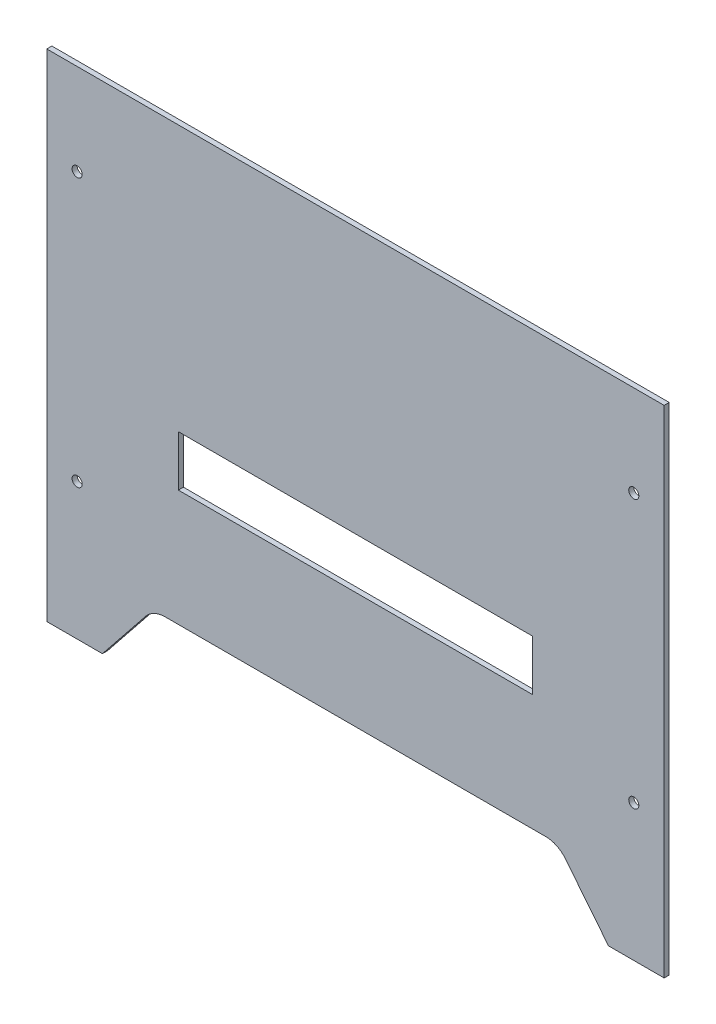
SolidWorks part; units mm, degrees
ref_plane "前视基准面" through (0, 0, 0) normal (0, 0, 1) x (1, 0, 0)
ref_plane "上视基准面" through (0, 0, 0) normal (0, 1, 0) x (1, 0, 0)
ref_plane "右视基准面" through (0, 0, 0) normal (1, 0, 0) x (0, 0, -1)
sketch "Sketch1" plane through (0, 0, 0) normal (0, 0, 1) x (1, 0, 0)
  line L0 (0, -98) -> (0, 0) construction
  line L1 (-122, -98) -> (122, -98) construction
  line L2 (-122, -98) -> (-122, 98)
  line L3 (-122, 98) -> (122, 98)
  line L4 (122, -98) -> (122, 98)
  line L5 (-122, -98) -> (122, 98) construction
  line L6 (-122, 98) -> (122, -98) construction
  line L7 (-75.1938, -73) -> (75.1938, -73)
  line L8 (83.0024, -76.753) -> (100, -98)
  line L9 (100, -98) -> (122, -98)
  line L10 (-100, -98) -> (-122, -98)
  line L11 (-83.0024, -76.753) -> (-100, -98)
  line L12 (110, -98) -> (110, 98) construction
  line L13 (-70, -27) -> (70, -27)
  line L14 (-70, -27) -> (-70, -7)
  line L15 (-70, -7) -> (70, -7)
  line L16 (70, -27) -> (70, -7)
  line L17 (-70, -27) -> (70, -7) construction
  line L18 (-70, -7) -> (70, -27) construction
  arc A0 (83.0024, -76.753) -> (75.1938, -73) centre (75.1938, -83) ccw
  arc A1 (-83.0024, -76.753) -> (-75.1938, -73) centre (-75.1938, -83) cw
  circle A2 centre (110, 62) radius 2
  circle A3 centre (110, -44) radius 2
  circle A4 centre (-110, -44) radius 2
  circle A5 centre (-110, 62) radius 2
  point P0 (0, 0)
  point P8 (0, -17)
  point P13 (80, -73)
  point P18 (0, -73)
  dimension "D6" = 10
  dimension "D11" = 4
  dimension "D12" = 4
  dimension "D1" = 244
  dimension "D2" = 196
  dimension "D3" = 25
  dimension "D4" = 22
  dimension "D5" = 80
  dimension "D7" = 140
  dimension "D8" = 20
  dimension "D9" = 105
  dimension "D10" = 12
  dimension "D13" = 36
  dimension "D14" = 106
extrude "Boss-Extrude1" add sketch "Sketch1" along normal blind 2
